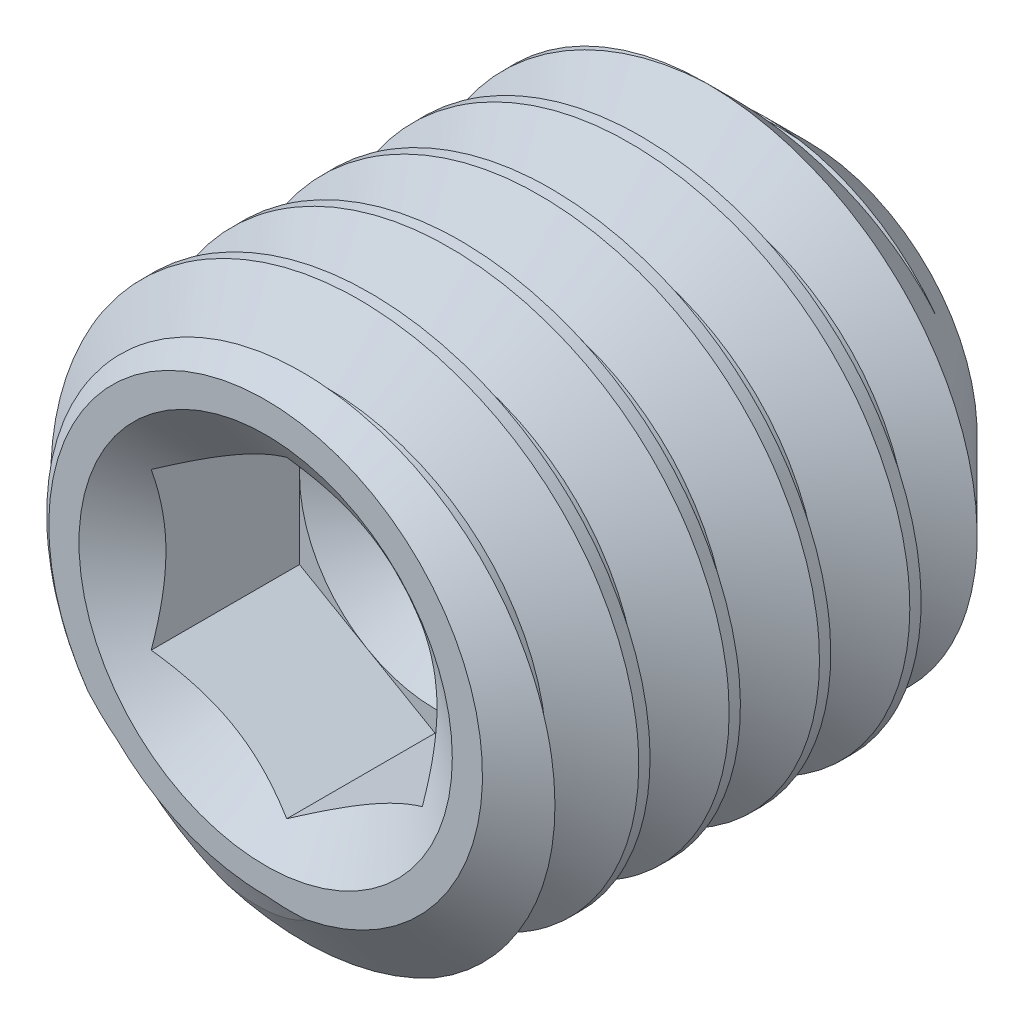
SolidWorks part; units mm, degrees
ref_plane "Front Plane" through (0, 0, 0) normal (0, 0, 1) x (1, 0, 0)
ref_plane "Top Plane" through (0, 0, 0) normal (0, 1, 0) x (1, 0, 0)
ref_plane "Right Plane" through (0, 0, 0) normal (1, 0, 0) x (0, 0, -1)
sketch "Sketch1" plane through (0, 0, 0) normal (1, 0, 0) x (0, 0, -1)
  line L0 (-1.2808, 0) -> (-1.2808, 1.2)
  line L1 (-1.2808, 1.2) -> (-1.0708, 1.5)
  line L2 (-1.0708, 1.5) -> (1.1567, 1.5)
  line L3 (1.1567, 1.5) -> (1.7192, 0.9375)
  line L5 (1.2808, 0) -> (-1.2808, 0)
  line L6 (1.2808, 0) -> (1.7192, 0) construction
  line L7 (1.7192, 0) -> (1.7192, 0.9375) construction
  line L8 (1.7192, -0.9375) -> (1.2808, 0) construction
  line L9 (-1.0708, -1.5) -> (1.1567, -1.5) construction
  line L10 (0, 0) -> (0, -0.5) construction
  line L11 (1.2808, 0) -> (1.612, 0.5512)
  line L12 (1.2808, 0) -> (1.612, -0.5512) construction
  arc A0 (1.612, 0.5512) -> (1.7192, 0.9375) centre (0.9692, 0.9375) ccw
  arc A1 (1.612, -0.5512) -> (1.7192, -0.9375) centre (0.9692, -0.9375) cw construction
  point P11 (-1.2808, 1.5)
  point P12 (-0.0308, -1.5)
  point P13 (-0.0308, -1.5)
  point P14 (1.7192, 1.5)
  dimension "D5" = 0.75
  dimension "Thread Size" = 3
  dimension "Length" = 3
  dimension "D3" = 35
  dimension "D6" = 45
  dimension "D7" = 2.4
  dimension "Thread Pitch" = 0.5
  dimension "D2" = 1.25
  dimension "D4" = 59
  dimension "D8" = 1.875
  dimension "D1" = 1.75
sketch "Sketch2" plane through (0, 0, 0) normal (0, 0, 1) x (1, 0, 0)
  line L1 (0.75, 0.433) -> (0, 0.866) construction
  line L2 (0, 0.866) -> (-0.75, 0.433) construction
  line L3 (-0.75, 0.433) -> (-0.75, -0.433) construction
  line L4 (-0.75, -0.433) -> (0, -0.866) construction
  line L5 (0, -0.866) -> (0.75, -0.433) construction
  line L6 (0.75, -0.433) -> (0.75, 0.433) construction
  circle A0 centre (0, 0) radius 0.75 construction
  circle A1 centre (0, 0) radius 1.5 construction
  dimension "Drive Size" = 1.5
sketch "Sketch4" plane through (0, 0, 0) normal (1, 0, 0) x (0, 0, -1)
  line L0 (1.2808, 0) -> (1.612, 0.5512) construction
  line L1 (-1.0708, 1.5) -> (1.1567, 1.5) construction
  line L2 (-1.2808, 0) -> (-1.2808, 1.2) construction
  line L3 (1.2808, 0) -> (-1.2808, 0) construction
  line L4 (1.2808, 0) -> (1.612, 0.5512)
  line L5 (1.1567, 1.5) -> (1.7192, 0.9375) construction
  line L6 (1.1567, 1.5) -> (1.7192, 0.9375)
  line L8 (1.2808, 0) -> (-1.2808, 0)
  line L9 (-1.2808, 0) -> (-1.2808, 1.2)
  line L10 (-1.0708, 1.5) -> (1.1567, 1.5)
  line L11 (-1.2808, 1.2) -> (-1.0708, 1.5) construction
  line L12 (-1.2808, 1.2) -> (-1.0708, 1.5)
  arc A0 (1.612, 0.5512) -> (1.7192, 0.9375) centre (0.9692, 0.9375) ccw construction
  arc A1 (1.612, 0.5512) -> (1.7192, 0.9375) centre (0.9692, 0.9375) ccw
revolve "Revolve1" add sketch "Sketch4" angle 360 about L8
sketch "Sketch6" plane through (0, 0, 1.2808) normal (0, 0, 1) x (1, 0, 0)
  line L1 (0.75, 0.433) -> (0, 0.866)
  line L2 (0, 0.866) -> (-0.75, 0.433)
  line L3 (-0.75, 0.433) -> (-0.75, -0.433)
  line L4 (-0.75, -0.433) -> (0, -0.866)
  line L5 (0, -0.866) -> (0.75, -0.433)
  line L6 (0.75, -0.433) -> (0.75, 0.433)
  circle A0 centre (0, 0) radius 0.75 construction
  dimension "D1" = 1.5
extrude "Cut-Extrude3" cut sketch "Sketch6" against normal blind 0.9375
sketch "Sketch7" plane through (0, 0, 1.2808) normal (0, 0, 1) x (1, 0, 0)
  line L0 (0, 0.866) -> (0, 1.2) construction
  circle A0 centre (0, 0) radius 1.033
  circle A2 centre (0, 0) radius 1.2 construction
  point P6 (0, 1.033)
  point P10 (0, 1.033)
extrude "Cut-Extrude4" cut sketch "Sketch7" against normal through all draft 55
sketch "Sketch8" plane through (0, 0, 0.3433) normal (0, 0, 1) x (1, 0, 0)
  circle A0 centre (0, 0) radius 0.75 construction
  circle A1 centre (0, 0) radius 0.75
extrude "Cut-Extrude5" cut sketch "Sketch8" against normal through all draft 60
ref_plane "Plane1" through (0, 0, -1.7192) normal (0, 0, 1) x (1, 0, 0)
sketch "Sketch9" plane through (0, 0, -1.7192) normal (0, 0, 1) x (1, 0, 0)
  circle A0 centre (0, 0) radius 1.5 construction
  circle A1 centre (0, 0) radius 1.5
curve "Helix/Spiral1" pitch 0.5 height 3.5 radius 1.5 centre (0, 0, -1.7192) axis (0, 0, 1) start towards (0, 1, 0)
sketch "Sketch10" plane through (0, 0, 0) normal (1, 0, 0) x (0, 0, -1)
  line L0 (1.7192, 1.5) -> (2.1567, 1.5)
  line L1 (2.1567, 1.5) -> (1.9692, 1.1752)
  line L2 (1.9067, 1.1752) -> (1.7192, 1.5)
  line L3 (1.9067, 1.1752) -> (1.9692, 1.1752)
  line L4 (1.9379, 1.1752) -> (1.9379, 1.5) construction
  line L5 (1.8129, 1.3376) -> (2.0629, 1.3376) construction
  point P10 (1.9379, 1.3376)
  dimension "D1" = 60
  dimension "D2" = 0.0625
  dimension "D3" = 0.25
sweep "Cut-Sweep1" cut profiles "Sketch10" path "Helix/Spiral1"
equation "\"D7@Sketch1\" = \"Thread Size@Sketch1\" * .8"
equation "\"D3\"= \"Length@Sketch1\" + \"Thread Pitch@Sketch1\""
equation "\"D4\"= \"Thread Pitch@Sketch1\""
equation "\"D1@Sketch6\"=\"Drive Size@Sketch2\""
equation "\"D1@Cut-Extrude3\"=\"Drive Size@Sketch2\"*.625"
equation "\"D3@Helix/Spiral1\"=\"Length@Sketch1\"+\"Thread Pitch@Sketch1\""
equation "\"D4@Helix/Spiral1\"=\"Thread Pitch@Sketch1\""
equation "\"D2@Sketch10\"=\"Thread Pitch@Sketch1\"/8"
equation "\"D3@Sketch10\"=\"Thread Pitch@Sketch1\"/2"
equation "\"D2@Sketch1\"=\"Thread Pitch@Sketch1\"*2.5"
equation "\"D5@Sketch1\"=\"Thread Size@Sketch1\"*.25"
equation "\"D8@Sketch1\"=\"Thread Size@Sketch1\"*.625"
equation "\"D1@Sketch1\"=\"Thread Pitch@Sketch1\"*3.5"
